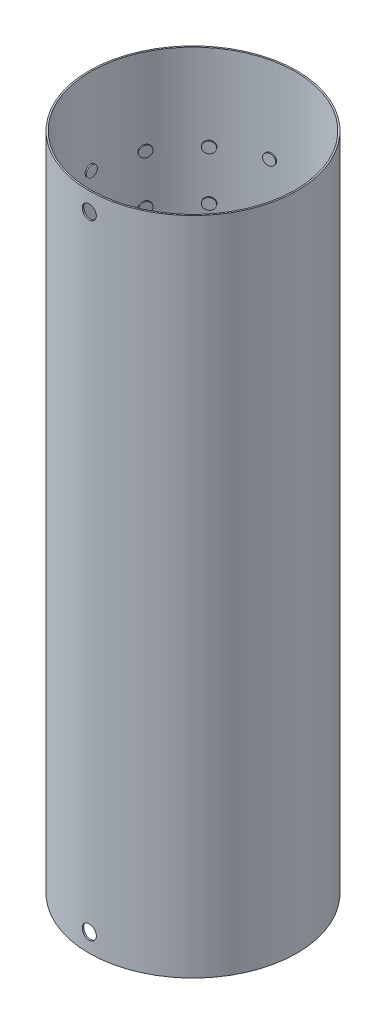
SolidWorks part; units mm, degrees
ref_plane "Front" through (0, 0, 0) normal (0, 0, 1) x (1, 0, 0)
ref_plane "Top" through (0, 0, 0) normal (0, 1, 0) x (1, 0, 0)
ref_plane "Right" through (0, 0, 0) normal (1, 0, 0) x (0, 0, -1)
sketch "Sketch1" plane through (0, 0, 0) normal (0, 1, 0) x (1, 0, 0)
  circle A0 centre (0, 0) radius 41.9
  circle A1 centre (0, 0) radius 42.5
  dimension "D1" = 83.8
  dimension "D2" = 85
extrude "Boss-Extrude1" add sketch "Sketch1" along normal blind 270
sketch "Sketch2" plane through (0, 0, 0) normal (1, 0, 0) x (0, 0, -1)
  line L0 (-42.5, 0) -> (42.5, 0) construction
  circle A0 centre (0, 135) radius 2.25
  circle A1 centre (0, 155) radius 2.25
  circle A2 centre (0, 175) radius 2.25
  circle A3 centre (0, 195) radius 2.25
  circle A4 centre (0, 215) radius 2.25
  circle A5 centre (0, 235) radius 2.25
  circle A6 centre (0, 115) radius 2.25
  circle A7 centre (0, 95) radius 2.25
  circle A8 centre (0, 75) radius 2.25
  circle A9 centre (0, 55) radius 2.25
  circle A10 centre (0, 35) radius 2.25
  dimension "D1" = 4.5
  dimension "D2" = 135
  dimension "D3" = 6
  dimension "D4" = 6
extrude "Boss-Extrude2" add sketch "Sketch2" along normal up to surface (41.8395 mm away)
pattern_circular "CirPattern2" count 14 over 360 about axis through (0, 270, 0) along (0, 1, 0) of "Boss-Extrude2"
sketch "Sketch4" plane through (0, 270, 0) normal (0, 1, 0) x (1, 0, 0)
  circle A0 centre (0, 0) radius 41.4
  circle A1 centre (0, 0) radius 41.9 construction
  dimension "D1" = 0.5
extrude "Cut-Extrude2" cut sketch "Sketch4" against normal through all
sketch "Sketch6" plane through (0, 0, 0) normal (0, 0, 1) x (1, 0, 0)
  line L0 (41.9, 270) -> (-41.9, 270) construction
  line L1 (-41.9, 0) -> (41.9, 0) construction
  circle A0 centre (0, 7.5) radius 2.875
  circle A1 centre (0, 262.5) radius 2.875
  dimension "D1" = 5.75
  dimension "D2" = 7.5
  dimension "D3" = 5.75
  dimension "D4" = 7.5
extrude "Cut-Extrude3" cut sketch "Sketch6" along normal through all
